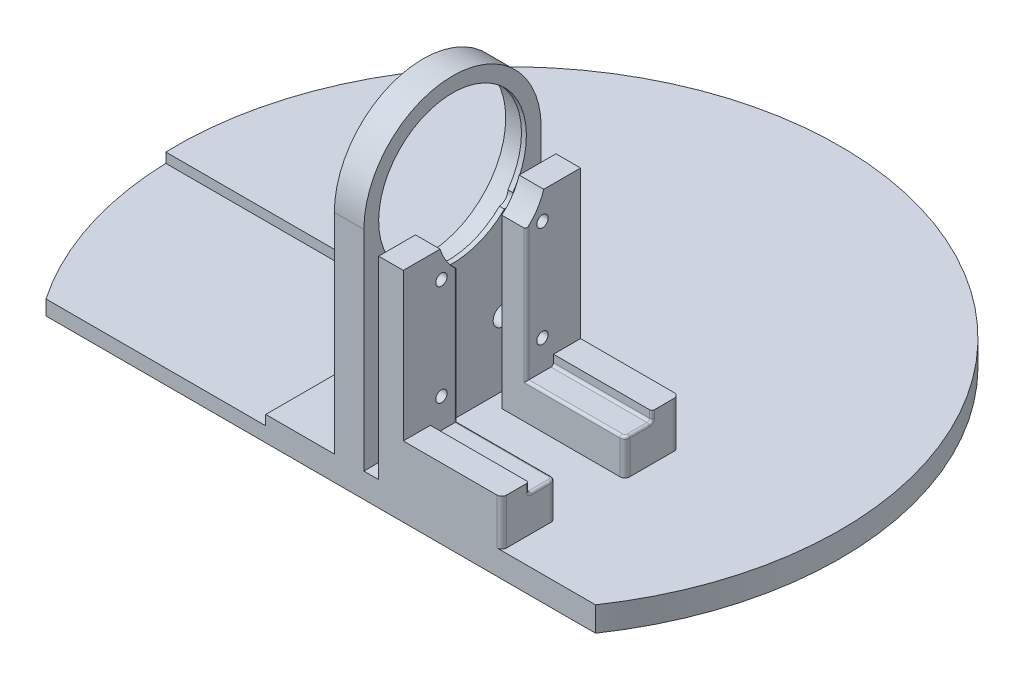
SolidWorks part; units mm, degrees
ref_plane "정면" through (0, 0, 0) normal (0, 0, 1) x (1, 0, 0)
ref_plane "윗면" through (0, 0, 0) normal (0, 1, 0) x (1, 0, 0)
ref_plane "우측면" through (0, 0, 0) normal (1, 0, 0) x (0, 0, -1)
sketch "스케치1" plane through (0, 0, 0) normal (0, 1, 0) x (1, 0, 0)
  circle A0 centre (0, 0) radius 67.5
  dimension "D1" = 135
extrude "보스-돌출1" add sketch "스케치1" along normal blind 5
sketch "스케치2" plane through (0, 5, 0) normal (0, 1, 0) x (1, 0, 0)
  line L1 (2.76, -2.5) -> (8.76, -2.5)
  line L2 (2.76, -2.5) -> (2.76, -37.5)
  line L3 (2.76, -37.5) -> (8.76, -37.5)
  line L4 (8.76, -2.5) -> (8.76, -37.5)
  point P4 (8.76, -20)
  dimension "D1" = 2.76
  dimension "D2" = 6
  dimension "D3" = 35
  dimension "D4" = 20
extrude "보스-돌출2" add sketch "스케치2" along normal blind 60
fillet "필렛1" radius 17.5 2 edges at (5.76, 65, 2.5) (5.76, 65, 37.5)
sketch "스케치3" plane through (2.76, 0, 0) normal (-1, 0, 0) x (0, 0, 1)
  circle A0 centre (20, 47.5) radius 16
  dimension "D1" = 32
extrude "컷-돌출1" cut sketch "스케치3" against normal blind 5
chamfer "모따기1" distance 0.8 angle 64 1 edges at (2.76, 47.5, 36) first distance on face at (7.76, 47.5, 36)
sketch "스케치4" plane through (7.76, 0, 0) normal (-1, 0, 0) x (0, 0, 1)
  circle A0 centre (20, 47.5) radius 15
  circle A1 centre (20, 47.5) radius 16 construction
  dimension "D1" = 1
extrude "컷-돌출2" cut sketch "스케치4" against normal through all
sketch "스케치6" plane through (8.76, 0, 0) normal (1, 0, 0) x (0, 0, -1)
  line L5 (-2.5, 27.5) -> (-2.5, 21.5)
  line L6 (-2.5, 27.5) -> (-4.5, 27.5)
  line L7 (-2.5, 21.5) -> (-4.5, 21.5)
  line L8 (-4.5, 27.5) -> (-4.5, 21.5)
  line L9 (-2.5, 47.5) -> (-2.5, 5) construction
  circle A0 centre (-20, 47.5) radius 15 construction
  dimension "D4" = 20
  dimension "D2" = 2
extrude "컷-돌출3" cut sketch "스케치6" against normal through all
sketch "스케치8" plane through (0, 0, 4.5) normal (0, 0, -1) x (-1, 0, 0)
  line L0 (-2.76, 27.5) -> (-8.76, 27.5) construction
  line L1 (-2.76, 27.5) -> (-2.76, 21.5) construction
  circle A0 centre (-5.76, 24.5) radius 1.6
  dimension "D1" = 3
  dimension "D2" = 3
  dimension "D3" = 3.2
extrude "컷-돌출5" cut sketch "스케치8" against normal blind 6
sketch "스케치9" plane through (0, 0, 4.5) normal (0, 0, -1) x (-1, 0, 0)
  line L0 (-2.76, 21.5) -> (-8.76, 21.5) construction
  line L3 (-4.3166, 27) -> (-7.2034, 27)
  line L4 (-7.2034, 27) -> (-8.6468, 24.5)
  line L5 (-8.6468, 24.5) -> (-7.2034, 22)
  line L6 (-7.2034, 22) -> (-4.3166, 22)
  line L7 (-4.3166, 27) -> (-2.76, 27)
  line L8 (-2.76, 27.5) -> (-2.76, 21.5) construction
  line L9 (-2.76, 27) -> (-2.76, 22)
  line L10 (-2.76, 22) -> (-4.3166, 22)
  line L12 (-2.8732, 24.5) -> (-4.3166, 27) [skipped]
  line L13 (-4.3166, 22) -> (-2.8732, 24.5) [skipped]
  circle A0 centre (-5.76, 24.5) radius 2.5 construction
  dimension "D1" = 5
extrude "컷-돌출8" cut sketch "스케치9" against normal blind 2.2 from offset 2 offset against normal yes
sketch "스케치11" plane through (0, 5, 0) normal (0, 1, 0) x (1, 0, 0)
  line L0 (11.76, -2.5) -> (36.76, -2.5)
  line L1 (11.76, -2.5) -> (11.76, -13)
  line L2 (36.76, -2.5) -> (36.76, -13)
  line L3 (11.76, -13) -> (36.76, -13)
  line L4 (11.76, -27) -> (36.76, -27)
  line L5 (11.76, -27) -> (11.76, -37.5)
  line L6 (36.76, -27) -> (36.76, -37.5)
  line L7 (11.76, -37.5) -> (36.76, -37.5)
  line L8 (8.76, -2.5) -> (2.76, -2.5) construction
  line L9 (8.76, -37.5) -> (8.76, -2.5) construction
  dimension "D1" = 35
  dimension "D2" = 10.5
  dimension "D3" = 3
  dimension "D4" = 25
extrude "보스-돌출4" add sketch "스케치11" along normal blind 7.3
sketch "스케치12" plane through (0, 12.3, 0) normal (0, 1, 0) x (1, 0, 0)
  line L0 (16.76, -32.5) -> (36.76, -32.5)
  line L1 (11.76, -2.5) -> (36.76, -2.5)
  line L2 (11.76, -2.5) -> (11.76, -13)
  line L3 (11.76, -13) -> (16.76, -13)
  line L4 (36.76, -2.5) -> (36.76, -7.5)
  line L5 (11.76, -27) -> (16.76, -27)
  line L6 (11.76, -27) -> (11.76, -37.5)
  line L7 (11.76, -37.5) -> (36.76, -37.5)
  line L8 (36.76, -32.5) -> (36.76, -37.5)
  line L9 (16.76, -7.5) -> (36.76, -7.5)
  line L10 (16.76, -7.5) -> (16.76, -13)
  line L11 (16.76, -27) -> (16.76, -32.5)
  line L12 (11.76, -13) -> (36.76, -13) construction
  line L13 (11.76, -27) -> (36.76, -27) construction
  line L14 (16.76, -2.5) -> (16.76, -13) construction
  line L15 (11.76, -7.5) -> (36.76, -7.5) construction
  line L16 (11.76, -32.5) -> (36.76, -32.5) construction
  line L17 (16.76, -27) -> (16.76, -37.5) construction
  dimension "D1" = 5.5
  dimension "D2" = 5.5
  dimension "D3" = 5
extrude "보스-돌출5" add sketch "스케치12" along normal blind 2
fillet "필렛3" radius 1 4 edges at (36.76, 8.65, 27) (36.76, 8.65, 13) (36.76, 9.65, 2.5) (36.76, 9.65, 37.5)
sketch "스케치13" plane through (16.76, 0, 0) normal (1, 0, 0) x (0, 0, -1)
  line L0 (-27, 14.3) -> (-37.5, 14.3)
  line L1 (-27, 14.3) -> (-27, 39.0147)
  line L2 (-37.5, 14.3) -> (-37.5, 44.3)
  line L3 (-30.5243, 44.3) -> (-37.5, 44.3)
  line L4 (-13, 14.3) -> (-2.5, 14.3)
  line L5 (-13, 14.3) -> (-13, 39.0147)
  line L6 (-2.5, 14.3) -> (-2.5, 44.3)
  line L7 (-9.4757, 44.3) -> (-2.5, 44.3)
  line L10 (-2.5, 21.5) -> (-2.5, 5) construction
  arc A0 (-30.5243, 44.3) -> (-27, 39.0147) centre (-20, 47.5) ccw
  arc A1 (-13, 39.0147) -> (-9.4757, 44.3) centre (-20, 47.5) ccw
  dimension "D2" = 22
  dimension "D1" = 30
extrude "보스-돌출6" add sketch "스케치13" against normal blind 5
sketch "스케치14" plane through (16.76, 0, 0) normal (1, 0, 0) x (0, 0, -1)
  line L1 (-30.25, 38.8) -> (-9.75, 38.8) construction
  line L2 (-30.25, 38.8) -> (-30.25, 18.3) construction
  line L3 (-30.25, 18.3) -> (-9.75, 18.3) construction
  line L4 (-9.75, 38.8) -> (-9.75, 18.3) construction
  line L8 (-32.5, 12.3) -> (-27, 12.3) construction
  circle A1 centre (-20, 47.5) radius 15 construction
  circle A2 centre (-30.25, 18.3) radius 1.15
  circle A3 centre (-9.75, 18.3) radius 1.15
  circle A4 centre (-9.75, 38.8) radius 1.15
  circle A5 centre (-30.25, 38.8) radius 1.15
  dimension "D5" = 2.3
  dimension "D1" = 20.5
  dimension "D2" = 20.5
  dimension "D3" = 6
  dimension "D4" = 10.25
extrude "컷-돌출10" cut sketch "스케치14" against normal through all
fillet "필렛2" radius 0.5 12 edges at (26.76, 12.3, 32.5) (26.76, 12.3, 7.5) (36.76, 13.3, 7.5) (36.76, 13.3, 32.5) (36.76, 12.3, 9.75) (36.76, 12.3, 30.25) (26.26, 12.3, 13) (36.4671, 12.3, 12.7071) (26.26, 12.3, 27) (36.4671, 12.3, 27.2929) (16.76, 25.6574, 13) (16.76, 25.6574, 27)
sketch "스케치15" plane through (2.76, 0, 0) normal (-1, 0, 0) x (0, 0, 1)
  circle A0 centre (9.75, 38.8) radius 2
  circle A1 centre (30.25, 38.8) radius 2
  circle A2 centre (9.75, 18.3) radius 2
  circle A3 centre (30.25, 18.3) radius 2
  dimension "D1" = 4
extrude "컷-돌출11" cut sketch "스케치15" against normal blind 10
sketch "스케치16" plane through (0, 5, 0) normal (0, 1, 0) x (1, 0, 0)
  line L0 (2.8284, -2.5) -> (2.8284, -20) construction
  line L1 (-11.1716, -2.5) -> (-67.5, -2.5)
  line L2 (-11.1716, -2.5) -> (-11.1716, -67.5)
  line L3 (-11.1716, -67.5) -> (-67.5, -67.5)
  line L4 (-67.5, -2.5) -> (-67.5, -67.5)
  line L6 (35.76, -2.5) -> (16.76, -2.5) construction
  circle A0 centre (0, 0) radius 67.5 construction
  dimension "D2" = 14
extrude "컷-돌출12" cut sketch "스케치16" against normal blind 2
sketch "스케치17" plane through (0, 5, 0) normal (0, 1, 0) x (1, 0, 0)
  line L0 (11.76, -37.5) -> (35.76, -37.5) construction
  line L1 (56.1249, -37.5) -> (-56.1249, -37.5)
  line L2 (56.1249, -37.5) -> (56.1249, -67.5)
  line L3 (56.1249, -67.5) -> (-56.1249, -67.5)
  line L4 (-56.1249, -37.5) -> (-56.1249, -67.5)
  arc A0 (-11.1716, -66.5691) -> (-67.4537, -2.5) centre (0, 0) ccw construction
extrude "컷-돌출13" cut sketch "스케치17" against normal through all
sketch "Sketch1" plane through (2.76, 0, 0) normal (-1, 0, 0) x (0, 0, 1)
  line L0 (20, 65) -> (2.0299, 65) construction
  line L1 (20, 63.5) -> (1.8038, 63.5) construction
  circle A0 centre (20, 47.5) radius 16 construction
  circle A1 centre (20, 47.5) radius 16 construction
sketch "Sketch2" plane through (2.76, 0, 0) normal (-1, 0, 0) x (0, 0, 1)
  line L0 (2, 27.5) -> (2, 47.5)
  line L1 (38, 5) -> (38, 47.5)
  line L2 (2.5, 45.2801) -> (2.5, 27.5) construction
  line L3 (37.5, 45.2801) -> (37.5, 5) construction
  line L4 (2.5, 47.5) -> (2.5, 45.2801) construction
  line L5 (37.5, 45.2801) -> (37.5, 47.5) construction
  line L6 (37.5, 45.2801) -> (37.5, 5)
  line L7 (2.5, 45.2801) -> (2.5, 27.5)
  line L8 (2.5, 47.5) -> (2.5, 45.2801)
  line L9 (37.5, 45.2801) -> (37.5, 47.5)
  line L10 (2.5, 27.5) -> (2, 27.5)
  line L13 (37.5, 5) -> (38, 5)
  line L16 (2.5, 21.5) -> (2, 21.5)
  line L17 (2.5, 21.5) -> (2.5, 5)
  line L18 (2.5, 5) -> (2, 5)
  line L19 (2, 21.5) -> (2, 5)
  line L20 (37.5, 5) -> (-67.5, 5) construction
  arc A3 (37.5, 47.5) -> (20, 65) centre (20, 47.5) ccw construction
  arc A4 (20, 65) -> (2.5, 47.5) centre (20, 47.5) ccw construction
  arc A5 (37.5, 47.5) -> (20, 65) centre (20, 47.5) ccw
  arc A6 (20, 65) -> (2.5, 47.5) centre (20, 47.5) ccw
  arc A7 (38, 47.5) -> (2, 47.5) centre (20, 47.5) ccw
  dimension "D1" = 0.5
  dimension "D2" = 0.5
extrude "Boss-Extrude1" add sketch "Sketch2" against normal up to surface (6 mm away) up to face at (8.76, 18.3, 11.75)
sketch "Sketch3" plane through (0, 0, 2.5) normal (0, 0, -1) x (-1, 0, 0)
  line L0 (-36.76, 5) -> (-36.76, 14.3) construction
  line L1 (-36.76, 5) -> (-36.76, 14.3)
  line L6 (-16.76, 14.3) -> (-35.76, 14.3)
  line L7 (-35.76, 14.3) -> (-35.76, 5)
  line L8 (-35.76, 5) -> (-11.76, 5)
  line L9 (-11.76, 5) -> (-11.76, 44.3)
  line L10 (-11.76, 44.3) -> (-16.76, 44.3)
  line L11 (-16.76, 44.3) -> (-16.76, 14.3)
  line L12 (-16.76, 14.3) -> (-36.76, 14.3)
  line L14 (-36.76, 5) -> (-11.76, 5)
  line L15 (-11.76, 5) -> (-11.76, 44.3)
  line L16 (-11.76, 44.3) -> (-16.76, 44.3)
  line L17 (-16.76, 44.3) -> (-16.76, 14.3)
  point P6 (-39.0929, 14.3)
  point P10 (-38.2105, 5)
  dimension "D1" = 0
extrude "Boss-Extrude2" add sketch "Sketch3" along normal up to surface (0.5 mm away) and the other way blind 3 up to face at (5.76, 13.25, 2)
fillet "Fillet1" radius 1 1 edges at (36.76, 9.65, 2)
sketch "Sketch4" plane through (0, 0, 37.5) normal (0, 0, 1) x (1, 0, 0)
  line L14 (11.76, 5) -> (8.76, 5)
  line L15 (8.76, 5) -> (2.76, 5)
  line L16 (2.76, 5) -> (-11.1716, 5)
  line L17 (-11.1716, 5) -> (-11.1716, 3)
  line L18 (-11.1716, 3) -> (-56.1249, 3)
  line L19 (-56.1249, 3) -> (-56.1249, 0)
  line L20 (-56.1249, 0) -> (56.1249, 0)
  line L21 (56.1249, 0) -> (56.1249, 5)
  line L22 (56.1249, 5) -> (35.76, 5)
  line L23 (35.76, 5) -> (35.76, 14.3)
  line L24 (35.76, 14.3) -> (16.76, 14.3)
  line L25 (16.76, 14.3) -> (16.76, 44.3)
  line L26 (16.76, 44.3) -> (11.76, 44.3)
  line L27 (11.76, 44.3) -> (11.76, 5)
  line L28 (11.76, 5) -> (8.76, 5)
  line L29 (8.76, 5) -> (2.76, 5)
  line L30 (2.76, 5) -> (-11.1716, 5)
  line L31 (-11.1716, 5) -> (-11.1716, 3)
  line L32 (-11.1716, 3) -> (-56.1249, 3)
  line L33 (-56.1249, 3) -> (-56.1249, 0)
  line L34 (-56.1249, 0) -> (56.1249, 0)
  line L35 (56.1249, 0) -> (56.1249, 5)
  line L36 (56.1249, 5) -> (35.76, 5)
  line L37 (35.76, 5) -> (35.76, 14.3)
  line L38 (35.76, 14.3) -> (16.76, 14.3)
  line L39 (16.76, 14.3) -> (16.76, 44.3)
  line L40 (16.76, 44.3) -> (11.76, 44.3)
  line L41 (11.76, 44.3) -> (11.76, 5)
  dimension "D1" = 0
extrude "Boss-Extrude3" add sketch "Sketch4" along normal up to surface (0.5 mm away) up to face at (5.76, 26.25, 38)
sketch "Sketch5" plane through (0, 0, 0) normal (0, -1, 0) x (1, 0, 0)
  line L0 (-67.5, 0) -> (-67.5, 58.6627) construction
  line L1 (0, -67.5) -> (-88.9466, -67.5) construction
  line L2 (-67.5, 0) -> (86.1174, 0) construction
  line L9 (0, -67.5) -> (0, 0) construction
  line L10 (67.5, 0) -> (67.5, 40.4766) construction
  circle A0 centre (0, 0) radius 67.5
  arc A3 (-56.1249, 37.5) -> (56.1249, 37.5) centre (0, 0) ccw construction
extrude "Cut-Extrude1" cut sketch "Sketch5" against normal blind 10 flip side to cut
sketch "Sketch6" plane through (0, 0, 38) normal (0, 0, 1) x (1, 0, 0)
  line L0 (36.76, 14.3) -> (36.76, 5) construction
  line L1 (36.76, 14.3) -> (36.76, 5)
  line L2 (36.76, 14.3) -> (34.6544, 14.3)
  line L3 (35.76, 14.3) -> (16.76, 14.3) construction
  line L4 (34.6544, 14.3) -> (34.6544, 5)
  line L5 (34.6544, 5) -> (36.76, 5)
extrude "Boss-Extrude4" add sketch "Sketch6" against normal blind 3
fillet "Fillet2" radius 1 1 edges at (36.76, 9.65, 38)
sketch "Sketch7" plane through (0, 5, 0) normal (0, 1, 0) x (1, 0, 0)
  line L0 (-11.1716, -38) -> (-11.1716, -2.5) construction
  line L1 (-11.1716, -2) -> (-11.1716, -2.5)
  line L2 (-11.1716, -2.5) -> (-67.4537, -2.5) construction
  line L3 (-11.1716, -2.5) -> (-67.4537, -2.5)
  line L4 (-11.1716, -2) -> (-67.4704, -2)
  arc A0 (55.7875, -38) -> (-67.4537, -2.5) centre (0, 0) ccw construction
  arc A1 (-67.4704, -2) -> (-67.4537, -2.5) centre (0, 0) ccw
  dimension "D1" = 0.5
extrude "Cut-Extrude2" cut sketch "Sketch7" against normal up to surface (2 mm away) up to face at (-37.0225, 3, 20.4558)
